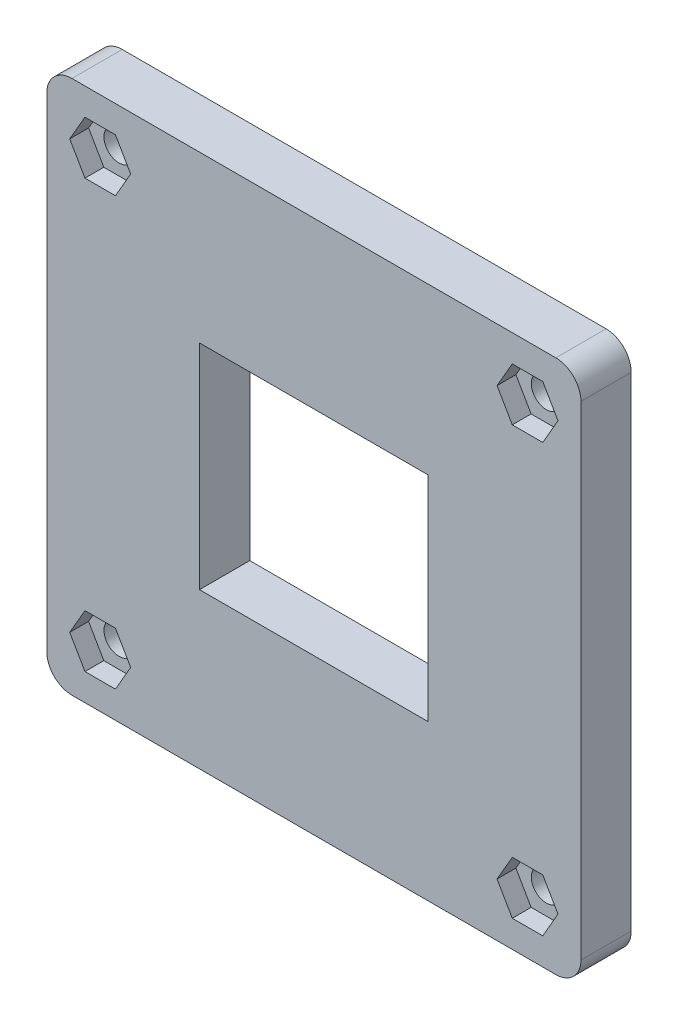
SolidWorks part; units mm, degrees
ref_plane "Front Plane" through (0, 0, 0) normal (0, 0, 1) x (1, 0, 0)
ref_plane "Top Plane" through (0, 0, 0) normal (0, 1, 0) x (1, 0, 0)
ref_plane "Right Plane" through (0, 0, 0) normal (1, 0, 0) x (0, 0, -1)
sketch "Sketch1" plane through (0, 0, 0) normal (0, 0, 1) x (1, 0, 0)
  line L4 (21.25, -19.25) -> (21.25, 19.25)
  line L5 (19.25, 21.25) -> (-19.25, 21.25)
  line L6 (-21.25, 19.25) -> (-21.25, -19.25)
  line L7 (-19.25, -21.25) -> (19.25, -21.25)
  line L8 (21.25, -19.25) -> (21.25, 19.25)
  line L9 (19.25, 21.25) -> (-19.25, 21.25)
  line L10 (-21.25, 19.25) -> (-21.25, -19.25)
  line L11 (-19.25, -21.25) -> (19.25, -21.25)
  line L21 (-8.9, -8.7) -> (8.9, -8.7) construction
  line L22 (-8.9, 7.9) -> (-8.9, -8.7) construction
  line L23 (8.9, 7.9) -> (-8.9, 7.9) construction
  line L24 (8.9, -8.7) -> (8.9, 7.9) construction
  line L25 (-8.9, -8.7) -> (8.9, -8.7) construction
  line L26 (-8.9, 7.9) -> (-8.9, -8.7) construction
  line L27 (8.9, 7.9) -> (-8.9, 7.9) construction
  line L28 (8.9, -8.7) -> (8.9, 7.9) construction
  line L29 (-9.1, -8.9) -> (9.1, -8.9)
  line L30 (9.1, -8.9) -> (9.1, 8.1)
  line L31 (9.1, 8.1) -> (-9.1, 8.1)
  line L32 (-9.1, 8.1) -> (-9.1, -8.9)
  circle A0 centre (-17, -17) radius 1.2 construction
  circle A1 centre (17, -17) radius 1.2 construction
  circle A2 centre (17, 17) radius 1.2 construction
  circle A3 centre (-17, 17) radius 1.2 construction
  arc A4 (21.25, 19.25) -> (19.25, 21.25) centre (19.25, 19.25) ccw
  arc A5 (-19.25, 21.25) -> (-21.25, 19.25) centre (-19.25, 19.25) ccw
  arc A6 (-21.25, -19.25) -> (-19.25, -21.25) centre (-19.25, -19.25) ccw
  arc A7 (19.25, -21.25) -> (21.25, -19.25) centre (19.25, -19.25) ccw
  arc A8 (21.25, 19.25) -> (19.25, 21.25) centre (19.25, 19.25) ccw
  arc A9 (-19.25, 21.25) -> (-21.25, 19.25) centre (-19.25, 19.25) ccw
  arc A10 (-21.25, -19.25) -> (-19.25, -21.25) centre (-19.25, -19.25) ccw
  arc A11 (19.25, -21.25) -> (21.25, -19.25) centre (19.25, -19.25) ccw
  circle A12 centre (-17, -17) radius 1.2
  circle A13 centre (17, -17) radius 1.2
  circle A14 centre (17, 17) radius 1.2
  circle A15 centre (-17, 17) radius 1.2
  point P31 (0, 0)
  point P34 (0, 0)
  dimension "D3" = 0.2
  dimension "D1" = 0
extrude "Boss-Extrude1" add sketch "Sketch1" along normal blind 4
sketch "Sketch2" plane through (0, 0, 0) normal (0, 0, -1) x (-1, 0, 0)
  line L0 (-9.5, 17) -> (9.5, 17) construction
  line L1 (-9.5, 18.25) -> (9.5, 18.25)
  line L2 (-9.5, 15.75) -> (9.5, 15.75)
  line L3 (-9.5, 16) -> (-9.5, 18) construction
  line L4 (9.5, 18) -> (9.5, 16) construction
  arc A0 (-9.5, 18.25) -> (-9.5, 15.75) centre (-9.5, 17) ccw
  arc A1 (9.5, 15.75) -> (9.5, 18.25) centre (9.5, 17) ccw
  point P2 (0, 17)
  point P7 (-17, 17)
  point P8 (0, 0)
  point P10 (0, 0)
  point P14 (0, 0)
  point P15 (0, 0)
  dimension "D1" = 2.5
extrude "Cut-Extrude3" cut sketch "Sketch2" against normal blind 1
sketch "Sketch3" plane through (0, 0, 4) normal (0, 0, 1) x (1, 0, 0)
  line L0 (-18.2124, -14.9) -> (-19.4249, -17)
  line L1 (15.7876, -14.9) -> (14.5751, -17)
  line L2 (14.5751, -17) -> (15.7876, -19.1)
  line L3 (15.7876, -19.1) -> (18.2124, -19.1)
  line L4 (18.2124, -19.1) -> (19.4249, -17)
  line L5 (19.4249, -17) -> (18.2124, -14.9)
  line L6 (18.2124, -14.9) -> (15.7876, -14.9)
  line L7 (-19.4249, -17) -> (-18.2124, -19.1)
  line L8 (-18.2124, -19.1) -> (-15.7876, -19.1)
  line L9 (-15.7876, -19.1) -> (-14.5751, -17)
  line L10 (-14.5751, -17) -> (-15.7876, -14.9)
  line L11 (-15.7876, -14.9) -> (-18.2124, -14.9)
  line L12 (-18.2124, 19.1) -> (-19.4249, 17)
  line L13 (-19.4249, 17) -> (-18.2124, 14.9)
  line L14 (-18.2124, 14.9) -> (-15.7876, 14.9)
  line L15 (-15.7876, 14.9) -> (-14.5751, 17)
  line L16 (-14.5751, 17) -> (-15.7876, 19.1)
  line L17 (-15.7876, 19.1) -> (-18.2124, 19.1)
  line L18 (15.7876, 19.1) -> (14.5751, 17)
  line L19 (14.5751, 17) -> (15.7876, 14.9)
  line L20 (15.7876, 14.9) -> (18.2124, 14.9)
  line L21 (18.2124, 14.9) -> (19.4249, 17)
  line L22 (19.4249, 17) -> (18.2124, 19.1)
  line L23 (18.2124, 19.1) -> (15.7876, 19.1)
  line L24 (15.7876, -14.9) -> (-18.2124, -14.9) construction
  line L25 (15.7876, -14.9) -> (15.7876, 19.1) construction
  circle A0 centre (17, -17) radius 2.1 construction
  circle A1 centre (-17, -17) radius 2.1 construction
  circle A2 centre (-17, 17) radius 2.1 construction
  circle A3 centre (17, 17) radius 2.1 construction
  point P1 (0, 0)
  point P11 (-17, 17)
  dimension "D1" = 4.2
  dimension "D2" = 2
  dimension "D4" = 90
  dimension "D3" = 2
extrude "Cut-Extrude4" cut sketch "Sketch3" against normal blind 1.5
